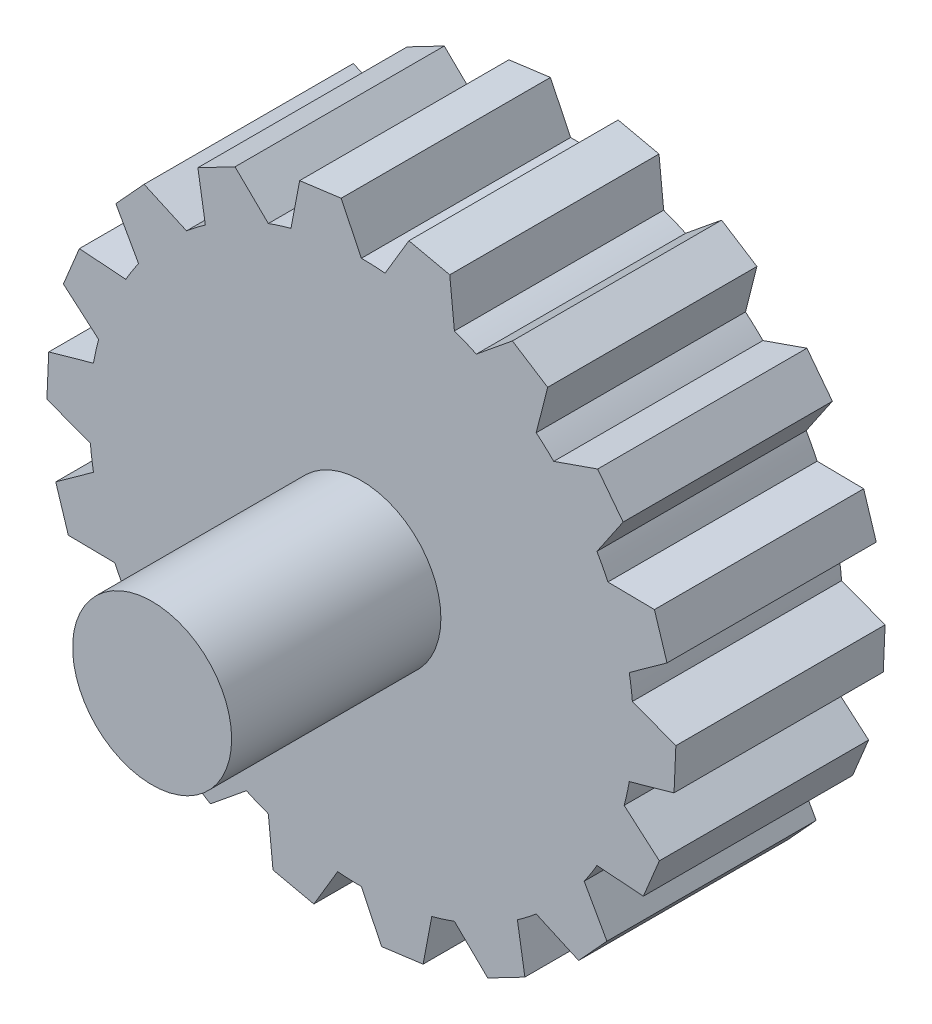
SolidWorks part; units mm, degrees
ref_plane "Front Plane" through (0, 0, 0) normal (0, 0, 1) x (1, 0, 0)
ref_plane "Top Plane" through (0, 0, 0) normal (0, 1, 0) x (1, 0, 0)
ref_plane "Right Plane" through (0, 0, 0) normal (1, 0, 0) x (0, 0, -1)
sketch "Sketch2" plane through (0, 0, 0) normal (0, 0, 1) x (1, 0, 0)
  circle A0 centre (0, 0) radius 1.9
  circle A1 centre (0, 0) radius 6.5
extrude "Boss-Extrude1" add sketch "Sketch2" along normal blind 10 contours A0
extrude "Boss-Extrude2" add sketch "Sketch2<3>" along normal blind 5 contours A1
sketch "Sketch2<3>" plane through (0, 0, 0) normal (0, 0, 1) x (1, 0, 0) same geometry as "Sketch2"
sketch "Sketch3" plane through (0, 0, 0) normal (0, 0, -1) x (-1, 0, 0)
  line L0 (0, 0) -> (0, 6.5) construction
  line L1 (0, 0) -> (1.6823, 6.2785) construction
  line L2 (0, 0) -> (0.9789, 7.4358) construction
  line L3 (0.4832, 7.5011) -> (1.4747, 7.3706)
  line L4 (1.4747, 7.3706) -> (1.6823, 6.2785)
  line L5 (0.4832, 7.5011) -> (0, 6.5)
  line L6 (3.0196, 6.8835) -> (2.2231, 6.108)
  line L7 (3.0196, 6.8835) -> (3.9066, 6.4217)
  line L8 (3.9066, 6.4217) -> (3.7282, 5.3245)
  line L9 (5.1918, 5.4356) -> (4.1781, 4.9793)
  line L10 (5.1918, 5.4356) -> (5.8674, 4.6983)
  line L11 (5.8674, 4.6983) -> (5.3245, 3.7282)
  line L12 (6.7378, 3.3321) -> (5.6292, 3.25)
  line L13 (6.7378, 3.3321) -> (7.1204, 2.4082)
  line L14 (7.1204, 2.4082) -> (6.2785, 1.6823)
  line L15 (7.4711, 0.8267) -> (6.4013, 1.1287)
  line L16 (7.4711, 0.8267) -> (7.5147, -0.1724)
  line L17 (7.5147, -0.1724) -> (6.4753, -0.5665)
  line L18 (7.3032, -1.7784) -> (6.4013, -1.1287)
  line L19 (7.3032, -1.7784) -> (7.0025, -2.7322)
  line L20 (7.0025, -2.7322) -> (5.891, -2.747)
  line L21 (6.2545, -4.169) -> (5.6292, -3.25)
  line L22 (6.2545, -4.169) -> (5.6458, -4.9624)
  line L23 (5.6458, -4.9624) -> (4.5962, -4.5962)
  line L24 (4.4514, -6.0568) -> (4.1781, -4.9793)
  line L25 (4.4514, -6.0568) -> (3.6081, -6.5941)
  line L26 (3.6081, -6.5941) -> (2.747, -5.891)
  line L27 (2.1114, -7.214) -> (2.2231, -6.108)
  line L28 (2.1114, -7.214) -> (1.1351, -7.4304)
  line L29 (1.1351, -7.4304) -> (0.5665, -6.4753)
  line L30 (-0.4832, -7.5011) -> (0, -6.5)
  line L31 (-0.4832, -7.5011) -> (-1.4747, -7.3706)
  line L32 (-1.4747, -7.3706) -> (-1.6823, -6.2785)
  line L33 (-3.0196, -6.8835) -> (-2.2231, -6.108)
  line L34 (-3.0196, -6.8835) -> (-3.9066, -6.4217)
  line L35 (-3.9066, -6.4217) -> (-3.7282, -5.3245)
  line L36 (-5.1918, -5.4356) -> (-4.1781, -4.9793)
  line L37 (-5.1918, -5.4356) -> (-5.8674, -4.6983)
  line L38 (-5.8674, -4.6983) -> (-5.3245, -3.7282)
  line L39 (-6.7378, -3.3321) -> (-5.6292, -3.25)
  line L40 (-6.7378, -3.3321) -> (-7.1204, -2.4082)
  line L41 (-7.1204, -2.4082) -> (-6.2785, -1.6823)
  line L42 (-7.4711, -0.8267) -> (-6.4013, -1.1287)
  line L43 (-7.4711, -0.8267) -> (-7.5147, 0.1724)
  line L44 (-7.5147, 0.1724) -> (-6.4753, 0.5665)
  line L45 (-7.3032, 1.7784) -> (-6.4013, 1.1287)
  line L46 (-7.3032, 1.7784) -> (-7.0025, 2.7322)
  line L47 (-7.0025, 2.7322) -> (-5.891, 2.747)
  line L48 (-6.2545, 4.169) -> (-5.6292, 3.25)
  line L49 (-6.2545, 4.169) -> (-5.6458, 4.9624)
  line L50 (-5.6458, 4.9624) -> (-4.5962, 4.5962)
  line L51 (-4.4514, 6.0568) -> (-4.1781, 4.9793)
  line L52 (-4.4514, 6.0568) -> (-3.6081, 6.5941)
  line L53 (-3.6081, 6.5941) -> (-2.747, 5.891)
  line L54 (-2.1114, 7.214) -> (-2.2231, 6.108)
  line L55 (-2.1114, 7.214) -> (-1.1351, 7.4304)
  line L56 (-1.1351, 7.4304) -> (-0.5665, 6.4753)
  circle A0 centre (0, 0) radius 6.5 construction
  arc A1 (1.6823, 6.2785) -> (0, 6.5) centre (0, 0) ccw
  arc A2 (3.7282, 5.3245) -> (2.2231, 6.108) centre (0, 0) ccw
  arc A3 (5.3245, 3.7282) -> (4.1781, 4.9793) centre (0, 0) ccw
  arc A4 (6.2785, 1.6823) -> (5.6292, 3.25) centre (0, 0) ccw
  arc A5 (6.4753, -0.5665) -> (6.4013, 1.1287) centre (0, 0) ccw
  arc A6 (5.891, -2.747) -> (6.4013, -1.1287) centre (0, 0) ccw
  arc A7 (4.5962, -4.5962) -> (5.6292, -3.25) centre (0, 0) ccw
  arc A8 (2.747, -5.891) -> (4.1781, -4.9793) centre (0, 0) ccw
  arc A9 (0.5665, -6.4753) -> (2.2231, -6.108) centre (0, 0) ccw
  arc A10 (-1.6823, -6.2785) -> (0, -6.5) centre (0, 0) ccw
  arc A11 (-3.7282, -5.3245) -> (-2.2231, -6.108) centre (0, 0) ccw
  arc A12 (-5.3245, -3.7282) -> (-4.1781, -4.9793) centre (0, 0) ccw
  arc A13 (-6.2785, -1.6823) -> (-5.6292, -3.25) centre (0, 0) ccw
  arc A14 (-6.4753, 0.5665) -> (-6.4013, -1.1287) centre (0, 0) ccw
  arc A15 (-5.891, 2.747) -> (-6.4013, 1.1287) centre (0, 0) ccw
  arc A16 (-4.5962, 4.5962) -> (-5.6292, 3.25) centre (0, 0) ccw
  arc A17 (-2.747, 5.891) -> (-4.1781, 4.9793) centre (0, 0) ccw
  arc A18 (-0.5665, 6.4753) -> (-2.2231, 6.108) centre (0, 0) ccw
  point P11 (0.9789, 7.4358)
  point P99 (0, 0)
  dimension "D1" = 18
extrude "Boss-Extrude3" add sketch "Sketch3" against normal blind 5
